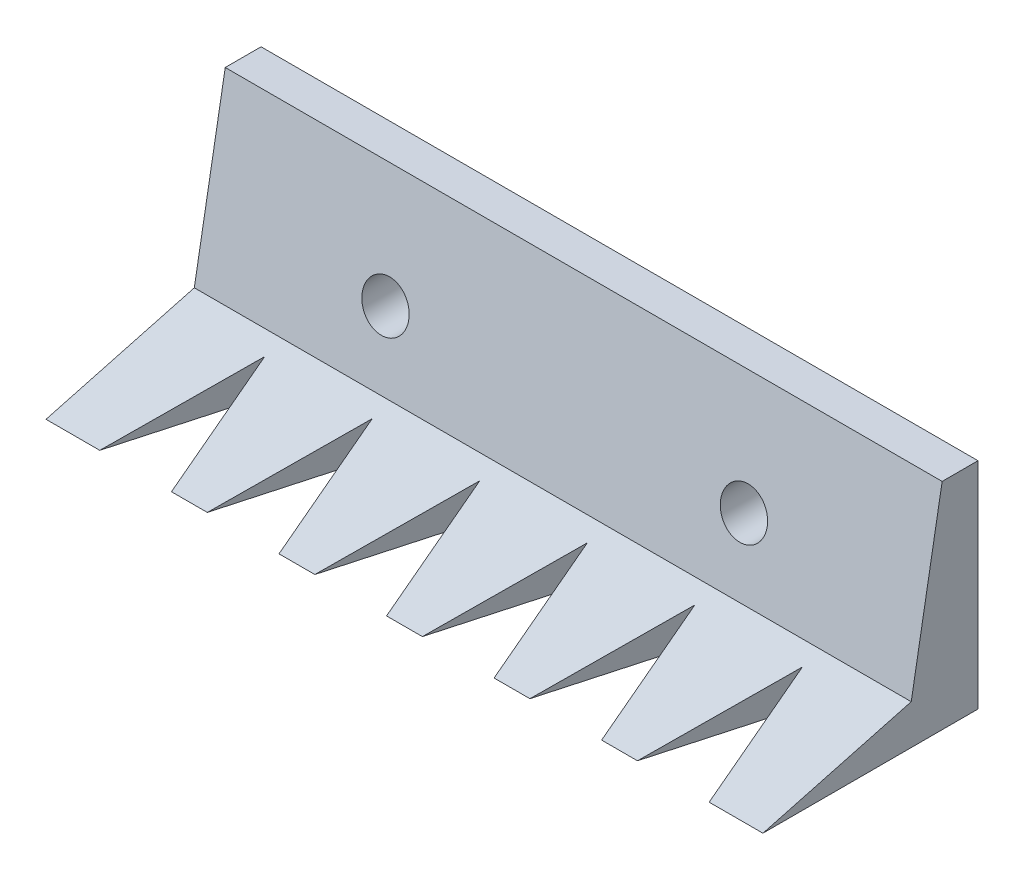
SolidWorks part; units mm, degrees
ref_plane "Front Plane" through (0, 0, 0) normal (0, 0, 1) x (1, 0, 0)
ref_plane "Top Plane" through (0, 0, 0) normal (0, 1, 0) x (1, 0, 0)
ref_plane "Right Plane" through (0, 0, 0) normal (1, 0, 0) x (0, 0, -1)
sketch "Sketch1" plane through (0, 0, 0) normal (1, 0, 0) x (0, 0, -1)
  line L0 (0, 0) -> (0, 30)
  line L3 (-30, 0) -> (0, 0)
  line L4 (-30, 0) -> (-9.3124, 5.5432)
  line L5 (-9.3124, 5.5432) -> (-5, 30)
  line L6 (-5, 30) -> (0, 30)
  dimension "D1" = 30
  dimension "D2" = 30
  dimension "D3" = 10
  dimension "D4" = 15
  dimension "D5" = 5
extrude "Boss-Extrude1" add sketch "Sketch1" along normal blind 100
sketch "Sketch2" plane through (0, 0, 0) normal (0, 0, -1) x (-1, 0, 0)
  line L0 (-100, 15) -> (0, 15) construction
  line L1 (-100, 0) -> (-100, 30) construction
  line L2 (0, 0) -> (0, 30) construction
  line L3 (-100, 30) -> (0, 30) construction
  point P8 (-75, 15)
  point P9 (-25, 15)
  dimension "D1" = 15
  dimension "D2" = 25
  dimension "D3" = 25
hole_wizard "M3 Clearance Hole1" positions "Sketch2" profile "Sketch3" hole size "M3" standard "ANSI Metric" end condition through all
sketch "Sketch3" plane through (25, 15, 0) normal (1, 0, 0) x (0, 1, 0)
  line L0 (0, 0) -> (0, 30)
  line L1 (0, 30) -> (1.7, 30)
  line L2 (1.7, 30) -> (1.7, 0)
  line L5 (1.7, 0) -> (0, 0)
  line L11 (0, -6.35) -> (0, 107.95) construction
  dimension "Thru Hole Dia." = 3.4
  dimension "Thru Hole Depth" = 30
ref_plane "Plane1" through (0, 0, 2.5) normal (0, 0, -1) x (-1, 0, 0)
sketch "Sketch4" plane through (0, 0, 2.5) normal (0, 0, -1) x (-1, 0, 0)
  circle A0 centre (-75, 15) radius 3.25
  circle A1 centre (-25, 15) radius 3.25
  dimension "D1" = 6.5
extrude "Cut-Extrude1" cut sketch "Sketch4" against normal through all
sketch "Sketch5" plane through (0, 0, 0) normal (0, 1, 0) x (1, 0, 0)
  line L0 (7.5, -30) -> (12.5, -12)
  line L1 (100, -30) -> (0, -30) construction
  line L2 (12.5, -12) -> (17.5, -30)
  line L3 (17.5, -30) -> (7.5, -30)
  dimension "D1" = 7.5
  dimension "D2" = 10
  dimension "D3" = 18
extrude "Cut-Extrude2" cut sketch "Sketch5" along normal through all both and the other way through all
pattern_linear "LPattern1" count 6 spacing 15 along (1, 0, 0) of "Cut-Extrude2"
